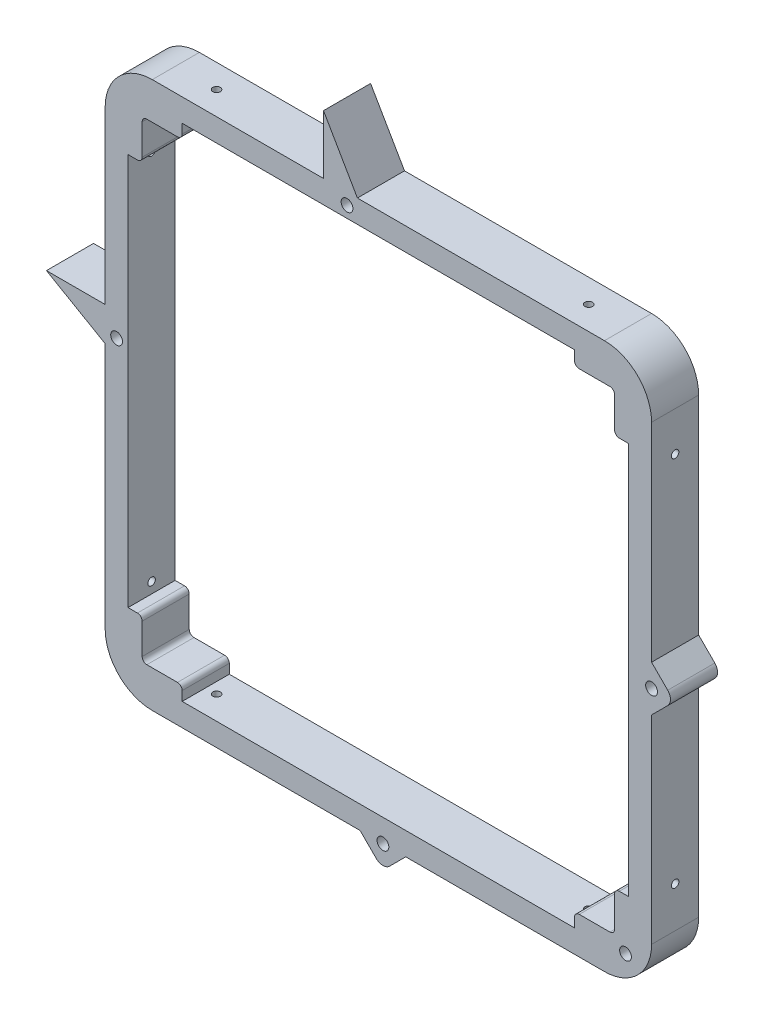
SolidWorks part; units mm, degrees
material "Nylon 101"
ref_plane "Front Plane" through (0, 0, 0) normal (0, 0, 1) x (1, 0, 0)
ref_plane "Top Plane" through (0, 0, 0) normal (0, 1, 0) x (1, 0, 0)
ref_plane "Right Plane" through (0, 0, 0) normal (1, 0, 0) x (0, 0, -1)
sketch "Sketch1" plane through (0, 0, 0) normal (0, 0, 1) x (1, 0, 0)
  line L13 (50.0019, -50.0019) -> (58, -58) construction
  line L14 (53, -41.5) -> (50.0019, -41.5)
  line L17 (41.5, -53) -> (41.5, -50.0019)
  line L18 (50.0019, -44.9586) -> (53, -44.9586)
  line L20 (53, -44.9586) -> (53, -53)
  line L23 (53, -53) -> (44.9586, -53)
  line L24 (44.9586, -53) -> (44.9586, -50.0019)
  line L25 (50.0019, -41.5) -> (50.0019, -50.0019)
  line L27 (50.0019, -50.0019) -> (41.5, -50.0019)
  line L35 (-41.5, 53) -> (41.5, 53)
  line L37 (50.0019, -50.0019) -> (50.0019, -41.5)
  line L38 (41.5, -50.0019) -> (50.0019, -50.0019)
  line L39 (53, -44.9586) -> (50.0019, -44.9586)
  line L40 (53, -53) -> (53, -44.9586)
  line L42 (44.9586, -53) -> (53, -53)
  line L43 (44.9586, -50.0019) -> (44.9586, -53)
  line L44 (53, -41.5) -> (50.0019, -41.5)
  line L45 (41.5, -53) -> (41.5, -50.0019)
  line L47 (53, -41.5) -> (53, 41.5)
  line L50 (41.5, -53) -> (-41.5, -53)
  line L52 (-41.5, -53) -> (-41.5, -50.0019)
  line L53 (-53, -41.5) -> (-50.0019, -41.5)
  line L54 (-44.96, -50.0019) -> (-44.96, -53)
  line L55 (-44.96, -53) -> (-53, -53)
  line L57 (-53, -53) -> (-53, -44.96)
  line L58 (-53, -44.96) -> (-50.0019, -44.96)
  line L59 (-41.5, -50.0019) -> (-50.0019, -50.0019)
  line L60 (-50.0019, -50.0019) -> (-50.0019, -41.5)
  line L61 (-53, -41.5) -> (-53, 41.5)
  line L63 (58, 58) -> (58, -58)
  line L65 (-50.0019, -50.0019) -> (-41.5, -50.0019)
  line L66 (-50.0019, -41.5) -> (-50.0019, -50.0019)
  line L67 (-44.96, -53) -> (-44.96, -50.0019)
  line L68 (-53, -53) -> (-44.96, -53)
  line L70 (-53, -44.96) -> (-53, -53)
  line L71 (-50.0019, -44.96) -> (-53, -44.96)
  line L72 (-41.5, -53) -> (-41.5, -50.0019)
  line L73 (-53, -41.5) -> (-50.0019, -41.5)
  line L75 (58, -58) -> (-58, -58)
  line L77 (-50.0019, -50.0019) -> (-58, -58) construction
  line L79 (-58, -58) -> (-58, 58)
  line L81 (-53, 41.5) -> (-50.0019, 41.5)
  line L82 (-41.5, 53) -> (-41.5, 50.0019)
  line L83 (-50.0019, 44.96) -> (-53, 44.96)
  line L84 (-53, 44.96) -> (-53, 53)
  line L86 (-53, 53) -> (-44.96, 53)
  line L87 (-44.96, 53) -> (-44.96, 50.0019)
  line L88 (-50.0019, 41.5) -> (-50.0019, 50.0019)
  line L89 (-50.0019, 50.0019) -> (-41.5, 50.0019)
  line L90 (-58, 58) -> (58, 58)
  line L94 (-50.0019, 50.0019) -> (-50.0019, 41.5)
  line L95 (-41.5, 50.0019) -> (-50.0019, 50.0019)
  line L96 (-53, 44.96) -> (-50.0019, 44.96)
  line L97 (-53, 53) -> (-53, 44.96)
  line L99 (-44.96, 53) -> (-53, 53)
  line L100 (-44.96, 50.0019) -> (-44.96, 53)
  line L101 (-53, 41.5) -> (-50.0019, 41.5)
  line L102 (-41.5, 53) -> (-41.5, 50.0019)
  line L106 (-50.0019, 50.0019) -> (-58, 58) construction
  line L110 (41.5, 53) -> (41.5, 50.0019)
  line L111 (53, 41.5) -> (50.0019, 41.5)
  line L112 (44.9586, 50.0019) -> (44.9586, 53)
  line L113 (44.9586, 53) -> (53, 53)
  line L115 (53, 53) -> (53, 44.96)
  line L116 (53, 44.96) -> (50.0019, 44.96)
  line L117 (41.5, 50.0019) -> (50.0019, 50.0019)
  line L118 (50.0019, 50.0019) -> (50.0019, 41.5)
  line L123 (50.0019, 50.0019) -> (41.5, 50.0019)
  line L124 (50.0019, 41.5) -> (50.0019, 50.0019)
  line L125 (44.9586, 53) -> (44.9586, 50.0019)
  line L126 (53, 53) -> (44.9586, 53)
  line L128 (53, 44.96) -> (53, 53)
  line L129 (50.0019, 44.96) -> (53, 44.96)
  line L130 (41.5, 53) -> (41.5, 50.0019)
  line L131 (53, 41.5) -> (50.0019, 41.5)
  line L135 (50.0019, 50.0019) -> (58, 58) construction
  point P2 (0, 58)
  point P4 (0, 53)
  point P6 (0, -53)
  point P7 (0, -58)
  point P10 (53, 0)
  point P11 (-53, 0)
  point P16 (-58, 0)
  point P17 (58, 0)
  dimension "D1" = 106
  dimension "D2" = 5
  dimension "D3" = 2.9981
extrude "base" add sketch "Sketch1" along normal mid plane 10 contours L20 L13 L14 L25 L18 | L13 L23 L24 L27 L17 | L13 L27 L24 L23 | L25 L13 L20 L18 | L117 L118 L116 L115 L113 L112 | L88 L89 L87 L86 L84 L83 | L59 L60 L58 L57 L55 L54 region at (51.5009, -45.0723, 0) region at (50.1156, 47.4809, 0) region at (-45.0737, -51.5009, 0) region at (-47.4809, 50.1156, 0) region at (56.3595, 0, 0)
ref_plane "Plane3" through (0, 0, 15) normal (0, 0, 1) x (1, 0, 0)
sketch "Sketch7" plane through (0, 0, 15) normal (0, 0, 1) x (1, 0, 0)
  line L0 (-41.65, 53.15) -> (41.65, 53.15)
  line L1 (41.65, 53.15) -> (41.65, 50.1519)
  line L2 (41.65, 50.1519) -> (50.1519, 50.1519)
  line L3 (50.1519, 50.1519) -> (50.1519, 41.65)
  line L4 (50.1519, 41.65) -> (53.15, 41.65)
  line L5 (53.15, 41.65) -> (53.15, -41.65)
  line L6 (53.15, -41.65) -> (50.1519, -41.65)
  line L7 (50.1519, -41.65) -> (50.1519, -50.1519)
  line L8 (50.1519, -50.1519) -> (41.65, -50.1519)
  line L9 (41.65, -50.1519) -> (41.65, -53.15)
  line L10 (41.65, -53.15) -> (-41.65, -53.15)
  line L11 (-41.65, -53.15) -> (-41.65, -50.1519)
  line L12 (-41.65, -50.1519) -> (-50.1519, -50.1519)
  line L13 (-50.1519, -50.1519) -> (-50.1519, -41.65)
  line L14 (-50.1519, -41.65) -> (-53.15, -41.65)
  line L15 (-53.15, -41.65) -> (-53.15, 41.65)
  line L16 (-53.15, 41.65) -> (-50.1519, 41.65)
  line L17 (-50.1519, 41.65) -> (-50.1519, 50.1519)
  line L18 (-50.1519, 50.1519) -> (-41.65, 50.1519)
  line L19 (-41.65, 50.1519) -> (-41.65, 53.15)
  line L21 (-41.5, 53) -> (41.5, 53) construction
  line L22 (-41.5, 53) -> (-41.5, 50.0019) construction
  line L23 (-50.0019, 50.0019) -> (-41.5, 50.0019) construction
  line L24 (-50.0019, 41.5) -> (-50.0019, 50.0019) construction
  line L25 (-53, 41.5) -> (-50.0019, 41.5) construction
  line L26 (-53, -41.5) -> (-53, 41.5) construction
  line L27 (-53, -41.5) -> (-50.0019, -41.5) construction
  line L28 (-50.0019, -50.0019) -> (-50.0019, -41.5) construction
  line L29 (-41.5, -50.0019) -> (-50.0019, -50.0019) construction
  line L30 (-41.5, -53) -> (-41.5, -50.0019) construction
  line L31 (41.5, -53) -> (-41.5, -53) construction
  line L32 (41.5, -53) -> (41.5, -50.0019) construction
  line L33 (50.0019, -41.5) -> (50.0019, -50.0019) construction
  line L34 (53, -41.5) -> (53, 41.5) construction
  line L35 (50.0019, 50.0019) -> (50.0019, 41.5) construction
  line L36 (53, 41.5) -> (50.0019, 41.5) construction
  line L37 (41.5, 50.0019) -> (50.0019, 50.0019) construction
  dimension "D1" = 0.15
  dimension "D2" = 0.15
  dimension "D3" = 0.15
  dimension "D4" = 0.15
  dimension "D5" = 0.15
  dimension "D6" = 0.15
  dimension "D7" = 0.15
  dimension "D8" = 0.15
  dimension "D9" = 0.15
  dimension "D10" = 0.15
  dimension "D11" = 0.15
  dimension "D12" = 0.15
  dimension "D13" = 0.15
  dimension "D14" = 0.15
  dimension "D15" = 0.15
  dimension "D16" = 0.15
  dimension "D17" = 0.15
ref_plane "arm plane" through (0, 0, 0) normal (0.7071, 0.7071, 0) x (0.7071, -0.7071, 0)
sketch "Sketch2" plane through (0, 0, 0) normal (0.7071, 0.7071, 0) x (0.7071, -0.7071, 0)
  line L4 (70.9255, 5) -> (82.0244, 5)
  line L5 (19.0244, 36) -> (8.0244, 47)
  line L6 (19.0244, 36) -> (8.0244, 36) construction
  line L8 (82.0244, 5) -> (82.0244, 47)
  line L9 (82.0244, 47) -> (8.0244, 47)
  line L13 (19.0244, 36) -> (70.9255, 36)
  line L14 (70.9255, 36) -> (70.9255, 5)
  dimension "D1" = 74
  dimension "D2" = 11
  dimension "D3" = 45
  dimension "D4" = 31
extrude "arm" add sketch "Sketch2" along normal mid plane 10
ref_plane "shim supports plane" through (0, 0, -5) normal (0, 0, -1) x (-1, 0, 0)
sketch "Sketch3" plane through (0, 0, 0) normal (0, 0, 1) x (1, 0, 0)
  line L1 (61.5355, -54.4645) -> (54.4645, -61.5355) construction
  line L6 (58, 58) -> (58, -50.9289) construction
  line L7 (50.9289, -58) -> (-58, -58) construction
  line L8 (9.9167, -16.9878) -> (46.6163, -53.6874) construction
  line L9 (58, -50.9289) -> (61.5355, -54.4645) construction
  line L10 (54.818, -61.8891) -> (61.8891, -54.818)
  line L11 (61.8891, -54.818) -> (58, -50.9289)
  line L12 (58, -50.9289) -> (58, -58)
  line L13 (58, -58) -> (50.9289, -58)
  line L14 (50.9289, -58) -> (54.818, -61.8891)
  dimension "D1" = 0.5
extrude "Cut-Extrude1" cut sketch "Sketch3" against normal through all
ref_plane "Plane2" through (0, 0, -5) normal (0, 0, -1) x (-1, 0, 0)
sketch "Sketch5" plane through (0, 0, -5) normal (0, 0, -1) x (-1, 0, 0)
  line L0 (-46.6163, -53.6874) -> (-43.0808, -50.1519)
  line L7 (-50.1519, -43.0808) -> (-53.6874, -46.6163)
  line L8 (-53.6874, -46.6163) -> (-53.6874, -53.6874)
  line L9 (-50.0019, -50.0019) -> (-58, -58) construction
  line L10 (-53.6874, -53.6874) -> (-46.6163, -53.6874)
  line L12 (-53.6874, -46.6163) -> (-58, -50.9289) construction
  line L14 (-50.1519, -41.65) -> (-50.1519, -50.1519) construction
  line L15 (-50.1519, -50.1519) -> (-41.65, -50.1519) construction
  line L16 (-50.1519, -43.0808) -> (-50.1519, -50.1519)
  line L17 (-50.1519, -50.1519) -> (-43.0808, -50.1519)
  dimension "D1" = 5
  dimension "D2" = 10
extrude "Boss-Extrude4" add sketch "Sketch5" along normal up to surface (31 mm away) contours L8 L10 L0 L7 | L7 L8 L10 L0 L17 L16 region at (50.1519, -53.5374, -5) up to face at (31.8021, -31.8021, -36)
extrude "clearance" cut sketch "Sketch7" against normal up to surface (20 mm away) up to face at (0, 0, -5)
sketch "Sketch10" plane through (0, 0, 0) normal (0, 1, 0) x (1, 0, 0)
  line L0 (41.65, 5) -> (41.65, -5) construction
  circle A0 centre (39.65, 0) radius 0.8
  circle A1 centre (-39.35, 0) radius 0.8
  point P5 (41.65, 0)
  dimension "D1" = 1.6
  dimension "D2" = 2
  dimension "D3" = 79
hole_wizard "M2x0.4 Tapped Hole1" positions "Sketch11" profile "Sketch12" tap size "M2x0.4" standard "ANSI Metric" end condition through all
sketch "Sketch11" plane through (0, 0, 0) normal (0, 1, 0) x (1, 0, 0)
  point P0 (-39.35, 0)
  point P2 (39.65, 0)
sketch "Sketch12" plane through (-39.35, 0, 0) normal (1, 0, 0) x (0, 0, -1)
  line L0 (0, 0) -> (0, 58)
  line L1 (0, 58) -> (0.8, 58)
  line L2 (0.8, 58) -> (0.8, 0)
  line L5 (0.8, 0) -> (0, 0)
  line L11 (0, -6.35) -> (0, 107.95) construction
  dimension "Thru Tap Drill Dia." = 1.6
  dimension "Thru Tap Drill Depth" = 58
cosmetic thread "Hole Thread1" parameters "D2"=2
cosmetic thread "Hole Thread2" parameters "D2"=2
mirror "Mirror1" about plane through (0, 0, 0) normal (0, 1, 0) of "M2x0.4 Tapped Hole1"
cosmetic thread "Hole Thread3" parameters "D2"=2
cosmetic thread "Hole Thread4" parameters "D2"=2
sketch "Sketch13" plane through (0, 0, 0) normal (1, 0, 0) x (0, 0, -1)
  line L2 (5, 41.65) -> (-5, 41.65) construction
  circle A0 centre (0, 39.65) radius 0.8
  circle A1 centre (0, -39.35) radius 0.8
  dimension "D1" = 1.6
  dimension "D3" = 79
  dimension "D2" = 2
hole_wizard "M2x0.4 Tapped Hole2" positions "Sketch14" profile "Sketch15" tap size "M2x0.4" standard "ANSI Metric" end condition through all
sketch "Sketch14" plane through (0, 0, 0) normal (1, 0, 0) x (0, 0, -1)
  point P0 (0, 39.65)
  point P3 (0, -39.35)
sketch "Sketch15" plane through (0, 39.65, 0) normal (0, 1, 0) x (0, 0, 1)
  line L0 (0, 0) -> (0, 58)
  line L1 (0, 58) -> (0.8, 58)
  line L2 (0.8, 58) -> (0.8, 0)
  line L5 (0.8, 0) -> (0, 0)
  line L11 (0, -6.35) -> (0, 107.95) construction
  dimension "Thru Tap Drill Dia." = 1.6
  dimension "Thru Tap Drill Depth" = 58
cosmetic thread "Hole Thread5" parameters "D2"=2
cosmetic thread "Hole Thread6" parameters "D2"=2
mirror "Mirror2" about plane through (0, 0, 0) normal (1, 0, 0) of "M2x0.4 Tapped Hole2"
cosmetic thread "Hole Thread7" parameters "D2"=2
cosmetic thread "Hole Thread8" parameters "D2"=2
sketch "Sketch16" plane through (0, 0, -5) normal (0, 0, -1) x (-1, 0, 0)
  line L0 (53.15, 11.65) -> (70.4705, 11.65)
  line L6 (53.15, -41.65) -> (53.15, 41.65) construction
  line L10 (-58, -58) -> (58, 58) construction
  line L18 (70.4705, 11.65) -> (53.15, 1.65)
  line L19 (53.15, 1.65) -> (53.15, 11.65)
  dimension "D1" = 20
  dimension "D2" = 10
  dimension "D3" = 30
extrude "extender" add sketch "Sketch16" along normal blind 28.6716 contours L19 L18 region at (-58.9235, 8.3167, -5)
ref_plane "Plane5" through (0, 0, -33.6716) normal (0, 0, -1) x (-1, 0, 0)
sketch "Sketch17" plane through (0, 0, -33.6716) normal (0, 0, -1) x (-1, 0, 0)
  line L2 (194.5714, 153.0714) -> (203.2316, 144.4111)
  line L4 (53.15, 1.65) -> (53.15, 11.65)
  line L5 (53.15, 11.65) -> (194.5714, 153.0714)
  line L9 (-50.9289, -58) -> (-2.1386, -9.2096) construction
  line L14 (203.2316, 144.4111) -> (70.4705, 11.65)
  line L15 (70.4705, 11.65) -> (53.15, 1.65)
  dimension "D2" = 200
extrude "angled horizontal" add sketch "Sketch17" along normal blind 10
sketch "Sketch21" plane through (0, 0, 0) normal (0, 0, 1) x (1, 0, 0)
  line L0 (-53.15, 1.65) -> (-53.15, 11.65)
  line L1 (-70.4705, 11.65) -> (-53.15, 11.65)
  line L2 (-70.4705, 11.65) -> (-53.15, 1.65)
  line L6 (-70.4705, 11.65) -> (-58, 4.4501) construction
  line L8 (3.8891, -3.8891) -> (-3.8891, 3.8891) construction
  line L9 (-11.65, 70.4705) -> (-1.65, 53.15)
  line L10 (-11.65, 70.4705) -> (-11.65, 53.15)
  line L11 (-1.65, 53.15) -> (-11.65, 53.15)
  line L12 (-53.15, 38.85) -> (-53.15, 40.45) construction
  line L14 (-53.15, 11.65) -> (-53.15, 1.65) construction
extrude "Arm Holder" add sketch "Sketch21" along normal up to surface (5 mm away) and the other way up to surface (5 mm away) up to face at (0, 0, 5) other way up to face at (-62.1568, 9.25, -5)
fillet "Fillet1" radius 1 12 edges at (50.1519, -41.65, 0) (41.65, -50.1519, 0) (-50.1519, -41.65, 0) (-41.65, -50.1519, 0) (-50.1519, 41.65, 0) (-41.65, 50.1519, 0) (41.65, 50.1519, 0) (50.1519, 41.65, 0) (50.1519, 50.1519, 0) (50.1519, -50.1519, -15.5) (-50.1519, -50.1519, 0) (-50.1519, 50.1519, 0)
fillet "Fillet2" radius 10 4 edges at (58, -58, -21) (58, 58, 0) (-58, 58, 0) (-58, -58, 0)
hole_wizard "M3x0.5 Tapped Hole2" positions "Sketch28" profile "Sketch29" tap size "M3x0.5" standard "ANSI Metric" end condition through all
sketch "Sketch28" plane through (0, 0, -47) normal (0, 0, -1) x (-1, 0, 0)
  line L1 (-57.6593, -50.5882) -> (-9.2096, -2.1386) construction
  arc A0 (-57.6593, -50.5882) -> (-50.5882, -57.6593) centre (-48, -48) ccw construction
  point P0 (-52.4654, -52.4654)
  point P11 (-55.0711, -55.0711)
  dimension "D1" = 5
  dimension "D2" = 3.685
cosmetic thread "Hole Thread13" parameters "D2"=3
sketch "Sketch29" plane through (52.4654, -52.4654, -47) normal (1, 0, 0) x (0, 1, 0)
  line L0 (0, 0) -> (0, 52)
  line L1 (0, 52) -> (1.25, 52)
  line L2 (1.25, 52) -> (1.25, 0)
  line L5 (1.25, 0) -> (0, 0)
  line L11 (0, -6.35) -> (0, 107.95) construction
  dimension "Thru Tap Drill Dia." = 2.5
  dimension "Thru Tap Drill Depth" = 52
hole_wizard "M3x0.5 Tapped Hole3" positions "Sketch36" profile "Sketch38" tap size "M3x0.5" standard "ANSI Metric"
sketch "Sketch36" plane through (0, 0, 5) normal (0, 0, 1) x (1, 0, 0)
  line L0 (-53.15, 41.65) -> (-53.15, -41.65) construction
  line L1 (-53.15, 11.65) -> (-53.15, 1.65) construction
  point P0 (-55.575, 6.65)
  point P9 (-53.15, 6.65)
  dimension "D1" = 2.425
sketch "Sketch38" plane through (-55.575, 6.65, 5) normal (1, 0, 0) x (0, -1, 0)
  line L0 (0, 0) -> (0, 30.5611)
  line L1 (0, 30.5611) -> (1.25, 29.81)
  line L2 (1.25, 29.81) -> (1.25, 0)
  line L5 (1.25, 0) -> (0, 0)
  line L10 (0, 30.5611) -> (-1.25, 29.81) construction
  line L11 (0, -6.35) -> (0, 107.95) construction
  dimension "Tap Drill Dia." = 2.5
  dimension "Tap Drill Depth" = 29.81
  dimension "Drill Angle" = 118
cosmetic thread "Hole Thread14" parameters "D1"=28.31, "D2"=3
mirror "U part of Outside arm" about plane through (0, 0, 0) normal (0.7071, 0.7071, 0) of "M3x0.5 Tapped Hole3", "angled horizontal", "extender"
cosmetic thread "Hole Thread15" parameters "D1"=28.31, "D2"=3
sketch "Sketch39" plane through (0, 0, 0) normal (0.7071, 0.7071, 0) x (0.7071, -0.7071, 0)
  line L0 (-58.068, 43.6716) -> (-245.8205, 43.6716) construction
  line L1 (-245.8205, 43.6716) -> (-241.8205, 43.6716)
  line L2 (-245.8205, 43.6716) -> (-245.8205, 33.6716)
  line L3 (-245.8205, 33.6716) -> (-241.8205, 33.6716)
  line L4 (-241.8205, 43.6716) -> (-241.8205, 33.6716)
  line L5 (-245.8205, 43.6716) -> (-241.8205, 33.6716) construction
  line L6 (-245.8205, 33.6716) -> (-241.8205, 43.6716) construction
  line L7 (-245.8205, 43.6716) -> (-245.8205, 33.6716) construction
  line L8 (-241.8205, 33.6716) -> (-231.8205, 43.6716)
  line L9 (-231.8205, 43.6716) -> (-241.8205, 43.6716)
  line L10 (-58.068, 33.6716) -> (-245.8205, 33.6716) construction
  point P0 (-243.8205, 38.6716)
  dimension "D1" = 4
  dimension "D2" = 45
extrude "Boss-Extrude18" add sketch "Sketch39" along normal up to next and the other way up to next contours L4 L1 L2 L3 | L8 L9 L4 region at (-172.4071, 172.4071, -38.6716) region at (-168.6359, 168.6359, -40.3383)
ref_plane "Plane12" through (0, 0, 0) normal (0.7071, -0.7071, 0) x (0, 0, -1)
ref_plane "Plane13" through (27.061, -27.061, 0) normal (0.7071, -0.7071, 0) x (0, 0, -1)
sketch "Sketch34" plane through (27.061, -27.061, 0) normal (0.7071, -0.7071, 0) x (0, 0, -1)
  line L0 (47, 5) -> (36, 5)
  line L1 (36, 5) -> (11, 36.8955)
  line L2 (5, 43.7544) -> (16, 43.7544)
  line L3 (22, 36.8955) -> (47, 5)
  line L4 (5, 5) -> (47, 5) construction
  line L6 (-5, 43.7544) -> (5, 43.7544) construction
  line L8 (5, 43.7544) -> (5, 36.8955)
  line L9 (5, 36.8955) -> (11, 36.8955)
  line L12 (22, 36.8955) -> (22, 43.7544)
  line L13 (22, 43.7544) -> (16, 43.7544)
  line L14 (5, 74.9533) -> (5, 7.0711) construction
  dimension "D2" = 6
extrude "Shim support arm" add sketch "Sketch34" along normal blind 6.85
sketch "Sketch35" plane through (0, 0, -5) normal (0, 0, -1) x (-1, 0, 0)
  line L7 (-62.8437, -0.9656) -> (-58, -5.8093)
  line L12 (-58, -5.8093) -> (-58, 3.878)
  line L13 (-58, -5.8093) -> (-58, 3.878) construction
  line L15 (-62.8437, -0.9656) -> (-58, 3.878) construction
  line L16 (-58, 3.878) -> (-62.8437, -0.9656)
extrude "Boss-Extrude17" add sketch "Sketch35" against normal up to surface (10 mm away) up to face at (-5.4, 55.575, 5)
mirror "Mirror4" about plane through (0, 0, 0) normal (0.7071, 0.7071, 0) of "Boss-Extrude17", "Shim support arm"
fillet "Fillet4" radius 2 8 edges at (30.5965, -23.5254, -41.5) (35.4402, -28.3691, -41.5) (28.3691, -35.4402, -41.5) (23.5254, -30.5965, -41.5) (3.3938, -55.5718, -22) (55.5718, -3.3938, -22) (0.9656, -62.8437, -8.5) (62.8437, -0.9656, -8.5)
hole_wizard "M3x0.5 Tapped Hole4" positions "Sketch40" profile "Sketch41" tap size "M3x0.5" standard "ANSI Metric" end condition through all
sketch "Sketch40" plane through (0, 0, -22) normal (0, 0, -1) x (-1, 0, 0)
  line L2 (3.878, -58) -> (48, -58) construction
  line L5 (-5.3274, -58.4819) -> (-2.3798, -61.4295) construction
  line L6 (-53.6382, -0.4838) -> (-58, 3.878) construction
  line L7 (-58, 48) -> (-58, 3.878) construction
  point P0 (-0.9656, -58)
  point P2 (-58, -0.9656)
  dimension "D1" = 3.425
  dimension "D2" = 3.425
sketch "Sketch41" plane through (0.9656, -58, -22) normal (1, 0, 0) x (0, 1, 0)
  line L0 (0, 0) -> (0, 27)
  line L1 (0, 27) -> (1.25, 27)
  line L2 (1.25, 27) -> (1.25, 0)
  line L5 (1.25, 0) -> (0, 0)
  line L11 (0, -6.35) -> (0, 107.95) construction
  dimension "Thru Tap Drill Dia." = 2.5
  dimension "Thru Tap Drill Depth" = 27
cosmetic thread "Hole Thread16" parameters "D2"=3
cosmetic thread "Hole Thread17" parameters "D2"=3
split "Split1" bodies to split 146 resulting bodies 142 split by face at (-42.9734, -42.3301, -5)
